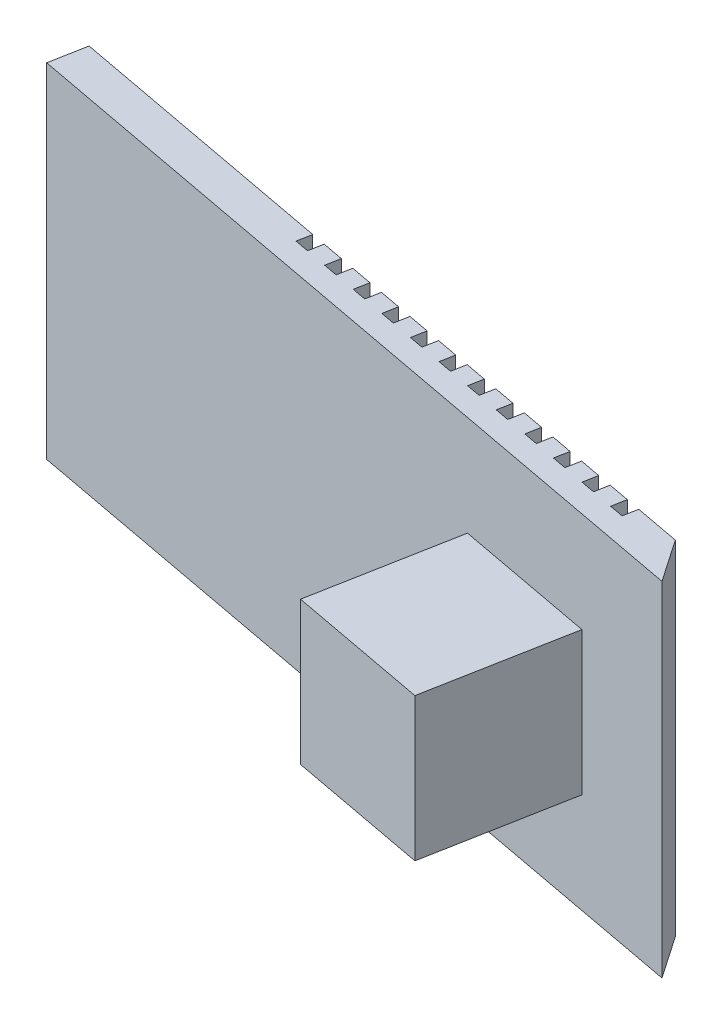
SolidWorks part; units mm, degrees
ref_plane "Front Plane" through (0, 0, 0) normal (0, 0, 1) x (1, 0, 0)
ref_plane "Top Plane" through (0, 0, 0) normal (0, 1, 0) x (1, 0, 0)
ref_plane "Right Plane" through (0, 0, 0) normal (1, 0, 0) x (0, 0, -1)
sketch "Sketch1" plane through (376.1936, 0, -2012.5744) normal (0.1837, 0, -0.983) x (-0.983, 0, -0.1837)
  line L8 (-990.0734, 471.7169) -> (-933.8257, 471.7169)
  line L9 (-933.8257, 471.7169) -> (-933.8257, 495.7169)
  line L10 (-933.8257, 495.7169) -> (-990.0734, 495.7169)
  line L11 (-990.0734, 495.7169) -> (-990.0734, 471.7169)
extrude "Boss-Extrude1" add sketch "Sketch1" along normal blind 2.54
chamfer "Chamfer1" distance 5 angle 45 1 edges at (1349.8777, 483.7169, -1833.1558)
sketch "Sketch2" plane through (376.6603, 0, -2015.0711) normal (0.1837, 0, -0.983) x (-0.983, 0, -0.1837)
  line L0 (-933.8257, 495.7169) -> (-985.0734, 495.7169) construction
  line L1 (-981.8776, 495.7169) -> (-980.8776, 495.7169)
  line L2 (-981.8776, 495.7169) -> (-981.8776, 471.7169)
  line L3 (-981.8776, 471.7169) -> (-980.8776, 471.7169)
  line L4 (-980.8776, 495.7169) -> (-980.8776, 471.7169)
  line L5 (-985.0734, 471.7169) -> (-933.8257, 471.7169) construction
  line L6 (-985.0734, 495.7169) -> (-985.0734, 471.7169) construction
  dimension "D1" = 3.1958
  dimension "D2" = 1
extrude "Cut-Extrude1" cut sketch "Sketch2" against normal blind 1
pattern_linear "LPattern1" count 12 spacing 2.5 along (-0.983, 0, -0.1837) of "Cut-Extrude1"
sketch "Sketch3" plane through (376.1936, 0, -2012.5744) normal (-0.1837, 0, 0.983) x (0.983, 0, 0.1837)
  line L0 (987.6134, 471.7169) -> (933.8257, 471.7169) construction
  line L1 (970.6134, 488.7169) -> (980.6134, 488.7169)
  line L2 (970.6134, 488.7169) -> (970.6134, 478.7169)
  line L3 (970.6134, 478.7169) -> (980.6134, 478.7169)
  line L4 (980.6134, 488.7169) -> (980.6134, 478.7169)
  line L5 (970.6134, 488.7169) -> (980.6134, 478.7169) construction
  line L6 (970.6134, 478.7169) -> (980.6134, 488.7169) construction
  line L7 (987.6134, 471.7169) -> (987.6134, 495.7169) construction
  point P0 (975.6134, 483.7169)
  dimension "D1" = 10
  dimension "D2" = 10
  dimension "D3" = 7
  dimension "D4" = 7
extrude "Boss-Extrude2" add sketch "Sketch3" along normal blind 10
